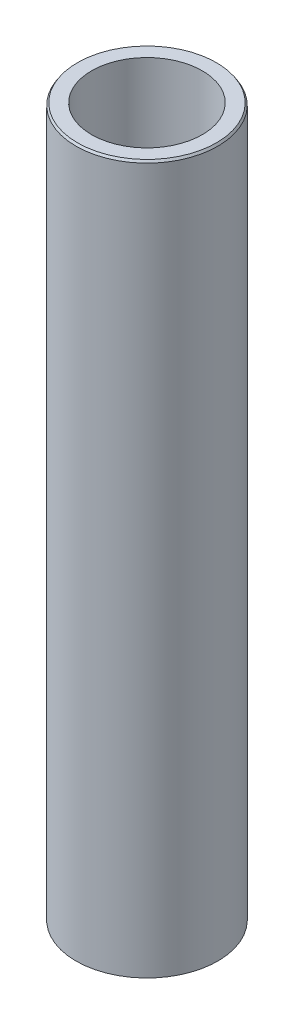
SolidWorks part; units mm, degrees
ref_plane "Front Plane" through (0, 0, 0) normal (0, 0, 1) x (1, 0, 0)
ref_plane "Top Plane" through (0, 0, 0) normal (0, 1, 0) x (1, 0, 0)
ref_plane "Right Plane" through (0, 0, 0) normal (1, 0, 0) x (0, 0, -1)
sketch "Sketch1" plane through (0, 0, 0) normal (0, 1, 0) x (1, 0, 0)
  circle A0 centre (0, 0) radius 60
  dimension "SHAFT_OD" = 120
extrude "Boss-Extrude1" add sketch "Sketch1" along normal blind 600
sketch "Sketch2" plane through (0, 0, 0) normal (0, 1, 0) x (1, 0, 0)
  circle A0 centre (0, 0) radius 46.8371
  dimension "BORE_D" = 93.6741
extrude "Cut-Extrude1" cut sketch "Sketch2" along normal through all
chamfer "Chamfer1" distance 1.8534 angle 33.64 2 edges at (0, 600, 60) (0, 0, 60) first distance on face at (0, 600, 60) first distance on face at (0, 0, 46.8371)
